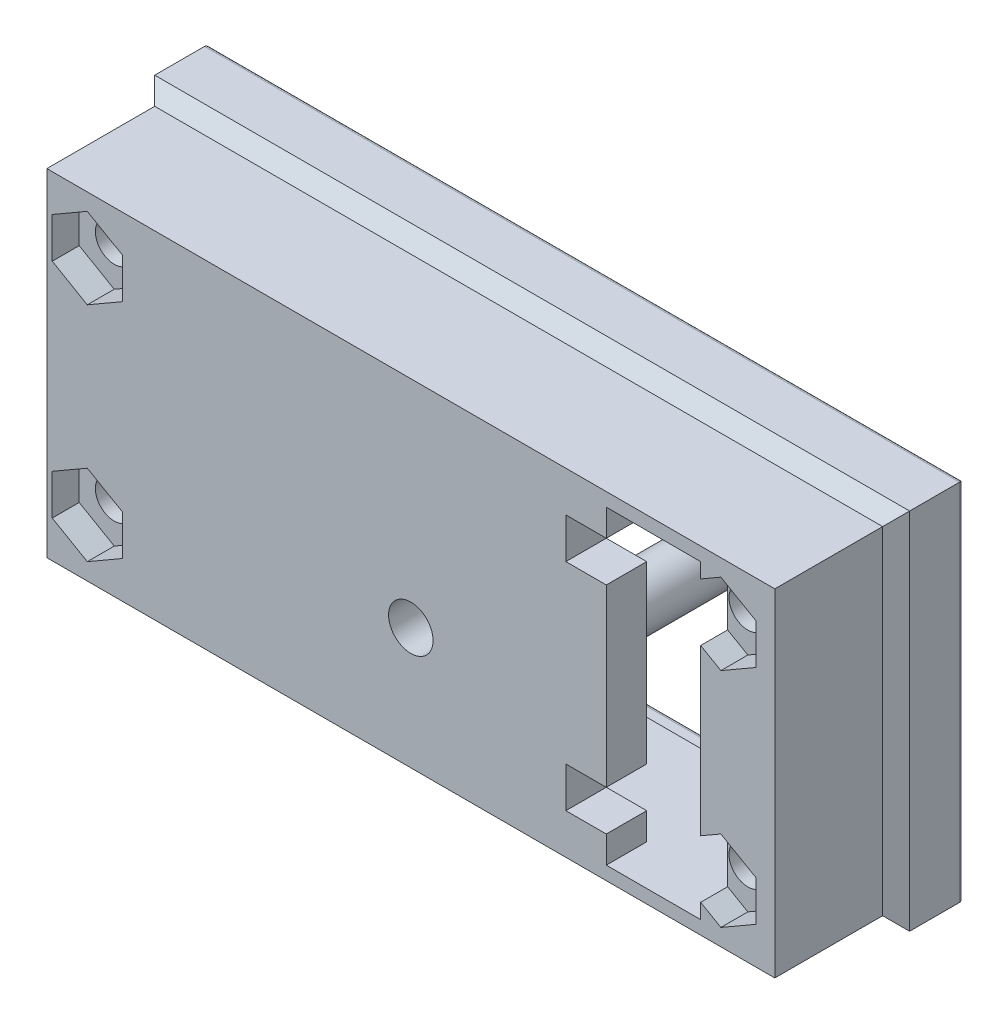
SolidWorks part; units mm, degrees
ref_plane "Front Plane" through (0, 0, 0) normal (0, 0, 1) x (1, 0, 0)
ref_plane "Top Plane" through (0, 0, 0) normal (0, 1, 0) x (1, 0, 0)
ref_plane "Right Plane" through (0, 0, 0) normal (1, 0, 0) x (0, 0, -1)
sketch "Sketch1" plane through (0, 0, 0) normal (0, 0, 1) x (1, 0, 0)
  line L1 (27, -12.5) -> (-27, -12.5)
  line L2 (27, -12.5) -> (27, 12.5)
  line L3 (27, 12.5) -> (-27, 12.5)
  line L4 (-27, -12.5) -> (-27, 12.5)
  line L5 (27, -12.5) -> (-27, 12.5) construction
  line L6 (27, 12.5) -> (-27, -12.5) construction
  line L7 (26, -11.5) -> (-26, -11.5)
  line L8 (26, -11.5) -> (26, 11.5)
  line L9 (26, 11.5) -> (-26, 11.5)
  line L10 (-26, -11.5) -> (-26, 11.5)
  line L11 (26, -11.5) -> (-26, 11.5) construction
  line L12 (26, 11.5) -> (-26, -11.5) construction
  point P0 (0, 0)
  point P6 (0, 0)
  dimension "D1" = 52
  dimension "D2" = 23
  dimension "D3" = 1
  dimension "D4" = 1
extrude "Boss-Extrude1" add sketch "Sketch1" along normal blind 8
sketch "Sketch2" plane through (0, 0, 8) normal (0, 0, 1) x (1, 0, 0)
  line L1 (27, -12.5) -> (-27, -12.5)
  line L2 (27, -12.5) -> (27, 12.5)
  line L3 (27, 12.5) -> (-27, 12.5)
  line L4 (-27, -12.5) -> (-27, 12.5)
  line L5 (27, -12.5) -> (-27, 12.5) construction
  line L6 (27, 12.5) -> (-27, -12.5) construction
  point P0 (0, 0)
extrude "Boss-Extrude2" add sketch "Sketch2" along normal blind 3
sketch "Sketch4" plane through (0, 0, 8) normal (0, 0, -1) x (-1, 0, 0)
  line L0 (26, -11.5) -> (-26, -11.5) construction
  line L1 (-21.5, 11.5) -> (-14.5, 11.5)
  line L2 (-21.5, 11.5) -> (-21.5, -11.5)
  line L3 (-21.5, -11.5) -> (-14.5, -11.5)
  line L4 (-14.5, 11.5) -> (-14.5, -11.5)
  line L5 (26, 11.5) -> (26, -11.5) construction
  line L6 (-26, 11.5) -> (26, 11.5) construction
  dimension "D1" = 7
  dimension "D2" = 40.5
extrude "Cut-Extrude1" cut sketch "Sketch4" against normal blind 3
sketch "Sketch5" plane through (0, 0, 8) normal (0, 0, -1) x (-1, 0, 0)
  circle A0 centre (-10, 0) radius 2
  dimension "D1" = 4
  dimension "D2" = 10
extrude "Boss-Extrude3" add sketch "Sketch5" along normal blind 9.7
fillet "Fillet1" radius 2 1 edges at (12, 0, 8)
sketch "Sketch6" plane through (0, 0, 8) normal (0, 0, -1) x (-1, 0, 0)
  line L0 (24, 8.25) -> (24, -8.25) construction
  line L1 (26, 11.5) -> (26, -11.5) construction
  line L2 (-23, 8.25) -> (-23, -8.25) construction
  line L3 (-26, -11.5) -> (-26, 11.5) construction
  line L4 (-27, -12.5) -> (-27, 12.5) construction
  circle A0 centre (24, 8.25) radius 1.4
  circle A1 centre (24, -8.25) radius 1.4
  circle A2 centre (-23, 8.25) radius 1.4
  circle A3 centre (-23, -8.25) radius 1.4
  point P4 (24, 0)
  point P6 (0, 0)
  point P17 (-23, 0)
  dimension "D2" = 2.8
  dimension "D3" = 2.8
  dimension "D4" = 2
  dimension "D5" = 16.5
  dimension "D6" = 4
  dimension "D1" = 16.5
extrude "Cut-Extrude2" cut sketch "Sketch6" against normal blind 10
sketch "Sketch8" plane through (0, 0, 11) normal (0, 0, 1) x (1, 0, 0)
  line L1 (-26.6, 9.7511) -> (-26.6, 6.7489)
  line L2 (-26.6, 6.7489) -> (-24, 5.2478)
  line L3 (-24, 5.2478) -> (-21.4, 6.7489)
  line L4 (-21.4, 6.7489) -> (-21.4, 9.7511)
  line L5 (-21.4, 9.7511) -> (-24, 11.2522)
  line L6 (-24, 11.2522) -> (-26.6, 9.7511)
  line L7 (-24, -5.2478) -> (-26.6, -6.7489)
  line L8 (-26.6, -6.7489) -> (-26.6, -9.7511)
  line L9 (-26.6, -9.7511) -> (-24, -11.2522)
  line L10 (-24, -11.2522) -> (-21.4, -9.7511)
  line L11 (-21.4, -9.7511) -> (-21.4, -6.7489)
  line L12 (-21.4, -6.7489) -> (-24, -5.2478)
  line L13 (23, 11.2522) -> (20.4, 9.7511)
  line L14 (-27, 12.5) -> (-27, -12.5) construction
  line L15 (20.4, 9.7511) -> (20.4, 6.7489)
  line L16 (20.4, 6.7489) -> (23, 5.2478)
  line L17 (23, 5.2478) -> (25.6, 6.7489)
  line L18 (25.6, 6.7489) -> (25.6, 9.7511)
  line L19 (25.6, 9.7511) -> (23, 11.2522)
  line L20 (23, -5.2478) -> (20.4, -6.7489)
  line L21 (20.4, -6.7489) -> (20.4, -9.7511)
  line L22 (20.4, -9.7511) -> (23, -11.2522)
  line L23 (23, -11.2522) -> (25.6, -9.7511)
  line L24 (25.6, -9.7511) -> (25.6, -6.7489)
  line L25 (25.6, -6.7489) -> (23, -5.2478)
  circle A0 centre (-24, 8.25) radius 2.6 construction
  circle A1 centre (-24, -8.25) radius 2.6 construction
  circle A2 centre (23, 8.25) radius 2.6 construction
  circle A3 centre (23, -8.25) radius 2.6 construction
  dimension "D2" = 5.2
extrude "Cut-Extrude3" cut sketch "Sketch8" against normal blind 2
sketch "Sketch10" plane through (0, 0, 8) normal (0, 0, -1) x (-1, 0, 0)
  line L1 (26, 11.5) -> (17.3098, 11.5)
  line L2 (26, 11.5) -> (26, 3.9581)
  line L3 (26, 3.9581) -> (17.3098, 3.9581)
  line L4 (17.3098, 11.5) -> (17.3098, 3.9581)
  line L5 (26, -11.5) -> (16.8129, -11.5)
  line L6 (26, -11.5) -> (26, -4.0462)
  line L7 (26, -4.0462) -> (16.8129, -4.0462)
  line L8 (16.8129, -11.5) -> (16.8129, -4.0462)
  line L9 (-26, 11.5) -> (-20.6838, 11.5)
  line L10 (-26, 11.5) -> (-26, 4.9094)
  line L11 (-26, 4.9094) -> (-20.6838, 4.9094)
  line L12 (-20.6838, 11.5) -> (-20.6838, 4.9094)
  line L13 (-26, -11.5) -> (-20.0802, -11.5)
  line L14 (-26, -11.5) -> (-26, -4.507)
  line L15 (-26, -4.507) -> (-20.0802, -4.507)
  line L16 (-20.0802, -11.5) -> (-20.0802, -4.507)
  circle A0 centre (24, 8.25) radius 1.4
  circle A1 centre (24, -8.25) radius 1.4
  circle A2 centre (24, -8.25) radius 2.4
  circle A3 centre (24, 8.25) radius 2.4
  circle A4 centre (24, 8.25) radius 1.4 construction
  circle A5 centre (-23, 8.25) radius 1.4
  circle A6 centre (-23, 8.25) radius 2.4
  circle A7 centre (-23, -8.25) radius 1.4
  circle A8 centre (-23, -8.25) radius 2.4
  circle M13 centre (24, 8.25) radius 1.4
  circle M14 centre (24, -8.25) radius 1.4
  dimension "D1" = 1
  dimension "D2" = 1
sketch "Sketch11" plane through (0, 0, 8) normal (0, 0, -1) x (-1, 0, 0)
  line L0 (-14.5, -11.5) -> (-14.5, 11.5) construction
  line L1 (-14.5, 9.5) -> (-11.5, 9.5)
  line L2 (-14.5, 9.5) -> (-14.5, 6.5)
  line L3 (-14.5, 6.5) -> (-11.5, 6.5)
  line L4 (-11.5, 9.5) -> (-11.5, 6.5)
  line L5 (-26, 11.5) -> (26, 11.5) construction
  line L6 (-14.5, -6.5) -> (-11.5, -6.5)
  line L7 (-14.5, -6.5) -> (-14.5, -9.5)
  line L8 (-14.5, -9.5) -> (-11.5, -9.5)
  line L9 (-11.5, -6.5) -> (-11.5, -9.5)
  line L10 (26, -11.5) -> (-14.5, -11.5) construction
  line L13 (27, -12.5) -> (-27, -12.5) construction
  circle A0 centre (0, -3.5) radius 1.65
  dimension "D1" = 3.3
  dimension "D6" = 9
  dimension "D2" = 3
  dimension "D3" = 3
  dimension "D4" = 2
  dimension "D5" = 2
extrude "Cut-Extrude4" cut sketch "Sketch11" against normal blind 10
extrude "Boss-Extrude5" add sketch "Sketch10" along normal blind 10 contours L2 A3 M13 | L6 A2 M14 region at (-25.9349, 8.25, 8) region at (-21.6651, -8.25, 8)
extrude "Boss-Extrude6" add sketch "Sketch10<5>" along normal blind 12.5 contours L10 A6 A5 | L14 A8 A7 region at (20.7511, 8.25, 8) region at (25.3321, -8.25, 8)
sketch "Sketch10<5>" plane through (0, 0, 8) normal (0, 0, -1) x (-1, 0, 0) same geometry as "Sketch10"
sketch "Sketch12" plane through (0, 0, 0) normal (0, 0, -1) x (-1, 0, 0)
  line L1 (-27, 12.5) -> (27, 12.5)
  line L2 (-27, 12.5) -> (-27, -12.5)
  line L3 (-27, -12.5) -> (27, -12.5)
  line L4 (27, 12.5) -> (27, -12.5)
  line L5 (-28, 13.5) -> (28, 13.5)
  line L6 (-28, 13.5) -> (-28, -13.5)
  line L7 (-28, -13.5) -> (28, -13.5)
  line L8 (28, 13.5) -> (28, -13.5)
  dimension "D1" = 1
  dimension "D2" = 1
  dimension "D3" = 1
  dimension "D4" = 1
extrude "Boss-Extrude7" add sketch "Sketch12" along normal blind 2 and the other way blind 2
sketch "Sketch14" plane through (0, 0, 8) normal (0, 0, -1) x (-1, 0, 0)
  line L0 (-14.5, -6.5) -> (-14.5, 6.5) construction
  line L1 (0, -0.2668) -> (-2.8, -1.8834)
  line L2 (-2.8, -1.8834) -> (-2.8, -5.1166)
  line L3 (-2.8, -5.1166) -> (0, -6.7332)
  line L4 (0, -6.7332) -> (2.8, -5.1166)
  line L5 (2.8, -5.1166) -> (2.8, -1.8834)
  line L6 (2.8, -1.8834) -> (0, -0.2668)
  line L7 (0, 2.0426) -> (-4.8, -0.7287)
  line L8 (-4.8, -0.7287) -> (-4.8, -6.2713)
  line L9 (-4.8, -6.2713) -> (0, -9.0426)
  line L10 (0, -9.0426) -> (4.8, -6.2713)
  line L11 (4.8, -6.2713) -> (4.8, -0.7287)
  line L12 (4.8, -0.7287) -> (0, 2.0426)
  circle A0 centre (0, -3.5) radius 2.8 construction
  circle A1 centre (0, -3.5) radius 4.8 construction
  dimension "D1" = 5.6
  dimension "D2" = 2
extrude "Boss-Extrude8" add sketch "Sketch14" along normal blind 3
fillet "Fillet2" radius 0.3 8 edges at (-27, 0, -2) (0, 12.5, -2) (27, 0, -2) (0, -12.5, -2) (0, 13.5, -2) (-28, 0, -2) (0, -13.5, -2) (28, 0, -2)
fillet "Fillet3" radius 0.3 12 edges at (8, 0, -1.7) (-21.6, -8.25, -2) (-26, -8.25, -2) (-25.4, -8.25, -2) (-21.6, 8.25, -2) (-26, 8.25, -2) (-25.4, 8.25, -2) (25.4, 8.25, -4.5) (21.6, 8.25, -4.5) (20.6, -8.25, -4.5) (21.6, -8.25, -4.5) (20.6838, 8.25, -4.5)
chamfer "Chamfer1" distance 1 angle 45 4 edges at (0, -12.5, 2) (27, 0, 2) (-27, 0, 2) (0, 12.5, 2)
